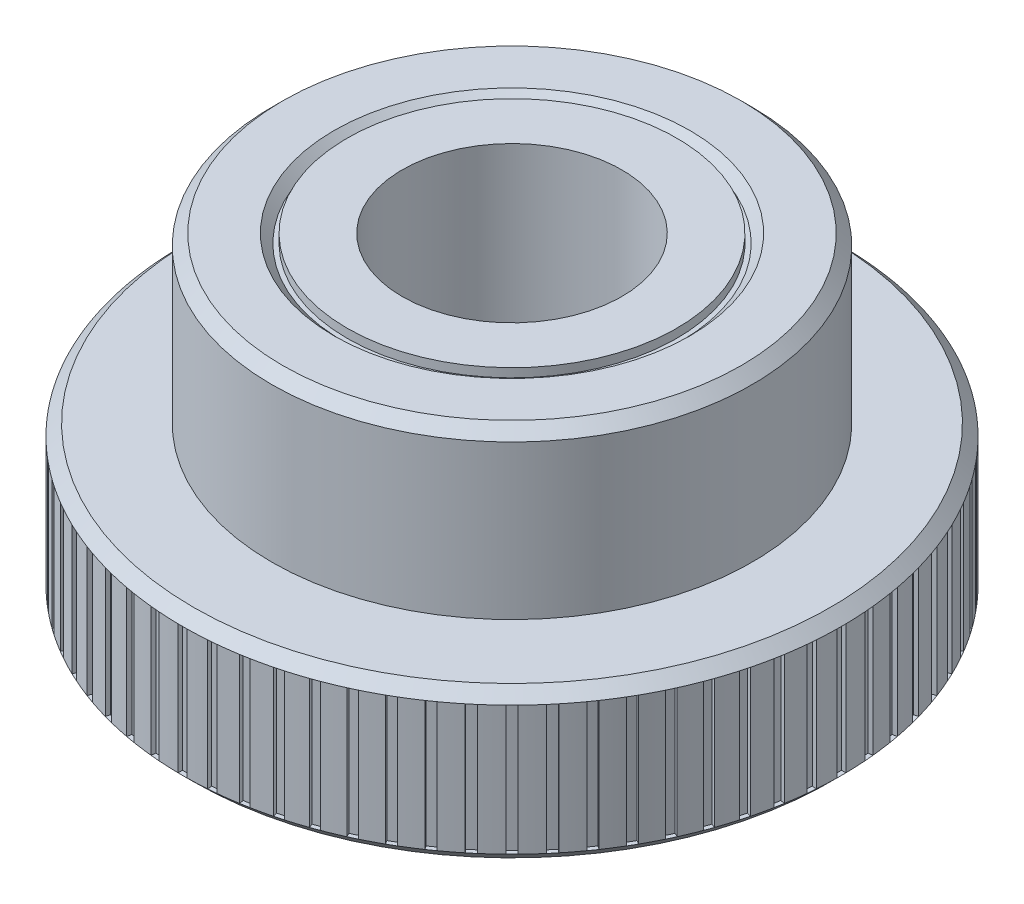
SolidWorks part; units mm, degrees
material "POM Acetal Copolymer"
ref_plane "Front Plane" through (0, 0, 0) normal (0, 0, 1) x (1, 0, 0)
ref_plane "Top Plane" through (0, 0, 0) normal (0, 1, 0) x (1, 0, 0)
ref_plane "Right Plane" through (0, 0, 0) normal (1, 0, 0) x (0, 0, -1)
sketch "Sketch1" plane through (0, 0, 0) normal (0, 0, 1) x (1, 0, 0)
  line L0 (0, 0) -> (0, 9.1281) construction
  line L1 (0, 9.1281) -> (-6.9453, 9.1281)
  line L2 (-9.525, 4.3656) -> (-9.525, 0)
  line L3 (-9.525, 0) -> (0, 0)
  line L4 (0, 0) -> (0, 9.1281)
  line L5 (0, 0) -> (0, -2.6189) construction
  line L6 (-5.5563, 4.3656) -> (-5.5563, 9.1281) construction
  line L7 (-9.525, 4.3656) -> (-6.9453, 4.3656)
  line L10 (-6.9453, 9.1281) -> (-6.9453, 4.3656)
  point P1 (0, 4.5641)
  dimension "D2" = 1.3891
revolve "Revolve1" add sketch "Sketch1" angle 360 about L0
sketch "Sketch3" plane through (0, 0, 0) normal (0, 1, 0) x (1, 0, 0)
  circle A0 centre (0, 0) radius 3.175
  dimension "OD" = 6.35
extrude "Cut-Extrude1" cut sketch "Sketch3" along normal through all
sketch "Sketch4" plane through (0, 0, 0) normal (0, 1, 0) x (1, 0, 0)
  circle A1 centre (0, 0) radius 3.175
  circle A2 centre (0, 0) radius 3.175
  dimension "D1" = 0
curve "Helix/Spiral1" pitch 1.27 height 15.4781 turns 12.1875 parameters "pitch"=1.27
sketch "Sketch21" plane through (0, 0, 0) normal (0, 1, 0) x (1, 0, 0)
  line L0 (0, 3.175) -> (0, 9.525)
  circle A0 centre (0, 0) radius 9.525 construction
  circle A1 centre (0, 0) radius 3.175 construction
  circle A2 centre (0, 0) radius 9.525 construction
  circle A3 centre (0, 0) radius 3.175 construction
  dimension "D1" = 6.35
chamfer "Chamfer1" distance 0.3175 angle 45 3 edges at (0, 9.1281, -6.9453) (0, 4.3656, -9.525) (0, 0, -9.525)
ref_plane "Plane1" through (0, 0, -12.7) normal (0, 0, 1) x (1, 0, 0)
sketch "Sketch17" plane through (0, 0, -12.7) normal (0, 0, 1) x (1, 0, 0)
  line L0 (-0.127, 0.3175) -> (-0.127, 4.0481)
  line L1 (9.525, 0.3175) -> (-9.525, 0.3175) construction
  line L2 (9.525, 4.0481) -> (-9.525, 4.0481) construction
  line L3 (0.127, 0.3175) -> (0.127, 4.0481)
  line L4 (0, 0.3175) -> (0, 4.0481) construction
  line L5 (-0.127, 0.3175) -> (0.127, 0.3175)
  line L6 (-0.127, 4.0481) -> (0.127, 4.0481)
  line L7 (0, 2.1828) -> (6.048, 2.1828) construction
  line L8 (0, 0) -> (0, 9.1281) construction
  line L9 (0, 0) -> (0, 9.1281) construction
  dimension "D2" = 0.254
extrude "Cut-Extrude6" cut sketch "Sketch17" along normal offset from surface (3.3028 mm away) 0.127 up to face at (0, 4.0481, -9.525) offset beyond the face yes
pattern_circular "CirPattern1" count 72 over 360 of "Cut-Extrude6" reverse direction yes
ref_plane "Plane3" through (0, 4.5641, 0) normal (0, 1, 0) x (-1, 0, 0)
sketch "Sketch22" plane through (0, 0, 0) normal (0, -1, 0) x (1, 0, 0)
  circle A0 centre (0, 0) radius 4.7625
  dimension "D1" = 9.525
extrude "Cut-Extrude-Thin1" cut sketch "Sketch22" against normal blind 0.254 thin thin type one direction wall 0.127
chamfer "Chamfer2" distance 0.254 angle 45 1 edges at (4.8895, 0, 0)
sketch "Sketch23" plane through (0, 9.1281, 0) normal (0, 1, 0) x (1, 0, 0)
  circle A1 centre (0, 0) radius 4.7625
  circle A2 centre (0, 0) radius 4.7625
  dimension "D1" = 0
extrude "Cut-Extrude-Thin2" cut sketch "Sketch23" against normal blind 0.254 thin thin type one direction wall 0.127
chamfer "Chamfer3" distance 0.254 angle 45 1 edges at (4.8895, 9.1281, 0)
sketch "Sketch5" [suppressed] plane through (0, 0, 0) normal (1, 0, 0) x (0, 0, -1)
  line L0 (-3.175, 0) -> (-3.175, -1.1113)
  line L1 (-3.175, -1.1113) -> (-2.3501, -0.635)
  line L2 (-2.3501, -0.635) -> (-2.3501, -0.4763)
  line L3 (-2.3501, -0.4763) -> (-3.175, 0)
  line L4 (-2.3501, -0.5556) -> (-3.175, -0.5556) construction
  line L5 (-2.7626, -0.8731) -> (-2.7626, -0.2381) construction
  line L6 (3.175, 0) -> (-3.175, 0) construction
  dimension "D1" = 0.1588
  dimension "D2" = 0.635
  dimension "D3" = 60
sweep "Sweep1" [suppressed] add profiles "Sketch5" path "Helix/Spiral1"
sketch "Sketch13" [suppressed] plane through (0, 0, 0) normal (0, -1, 0) x (1, 0, 0)
  circle A1 centre (0, 0) radius 4.7625
  circle A2 centre (0, 0) radius 4.7625
  dimension "D1" = 0
extrude "Cut-Extrude2" [suppressed] cut sketch "Sketch13" along normal through all
sketch "Sketch14" [suppressed] plane through (0, 9.1281, 0) normal (0, 1, 0) x (1, 0, 0)
  circle A0 centre (0, 0) radius 9.525 construction
  circle A1 centre (0, 0) radius 9.525
extrude "Cut-Extrude3" [suppressed] cut sketch "Sketch14" along normal through all
sketch "Sketch15" [suppressed] plane through (0, 0, 0) normal (0, -1, 0) x (1, 0, 0)
  circle A0 centre (0, 0) radius 3.175 construction
  circle A1 centre (0, 0) radius 3.175
extrude "Cut-Extrude4" [suppressed] cut sketch "Sketch15" against normal through all draft 45
sketch "Sketch16" [suppressed] plane through (0, 9.1281, 0) normal (0, 1, 0) x (1, 0, 0)
  circle A0 centre (0, 0) radius 3.175 construction
  circle A1 centre (0, 0) radius 3.175
extrude "Cut-Extrude5" [suppressed] cut sketch "Sketch16" against normal through all draft 45
ref_axis "Center Axis 1" through (0, 10.1697, 0) along (0, -1, 0)
ref_plane "Contact Plane 1" through (0, 9.1281, 0) normal (0, 1, 0) x (1, 0, 0)
equation "\"D1@Sketch5\" = \"pitch@Helix/Spiral1\"*.125"
equation "\"D2@Sketch5\" = \"pitch@Helix/Spiral1\"*.5"
equation "\"D1@Chamfer1\" = \"pitch@Helix/Spiral1\"*.25"
equation "\"D3@Helix/Spiral1\" = \"B@Sketch1\"+.250"
equation "\"D2@Sketch1\" = \"C@Sketch1\"*.1"
equation "\"D1@Sketch22\" = \"A@Sketch1\"*.5"
